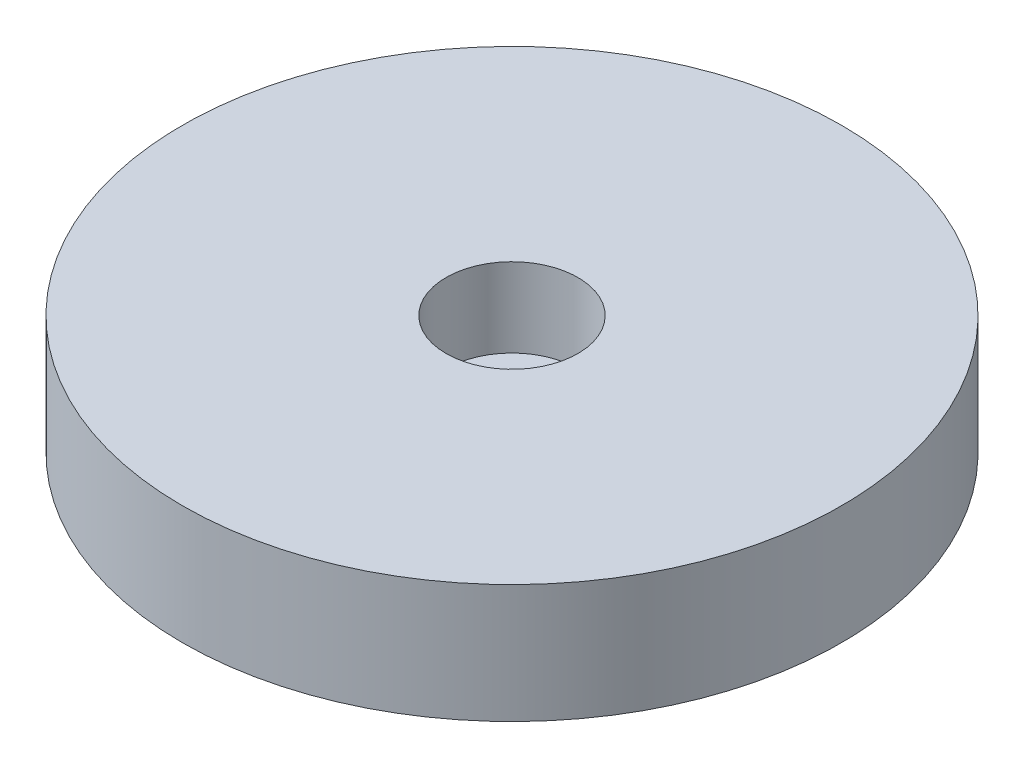
SolidWorks part; units mm, degrees
ref_plane "Alzado" through (0, 0, 0) normal (0, 0, 1) x (1, 0, 0)
ref_plane "Planta" through (0, 0, 0) normal (0, 1, 0) x (1, 0, 0)
ref_plane "Vista lateral" through (0, 0, 0) normal (1, 0, 0) x (0, 0, -1)
sketch "Croquis1" plane through (0, 0, 0) normal (0, 1, 0) x (1, 0, 0)
  circle A0 centre (0, 0) radius 25
  circle A1 centre (0, 0) radius 3.1
  dimension "D1" = 50
  dimension "D2" = 6.2
extrude "Saliente-Extruir1" add sketch "Croquis1" along normal blind 9
sketch "Croquis3" plane through (0, 9, 0) normal (0, 1, 0) x (1, 0, 0)
  circle A0 centre (0, 0) radius 5
  dimension "D1" = 10
extrude "Cortar-Extruir1" cut sketch "Croquis3" against normal blind 6
